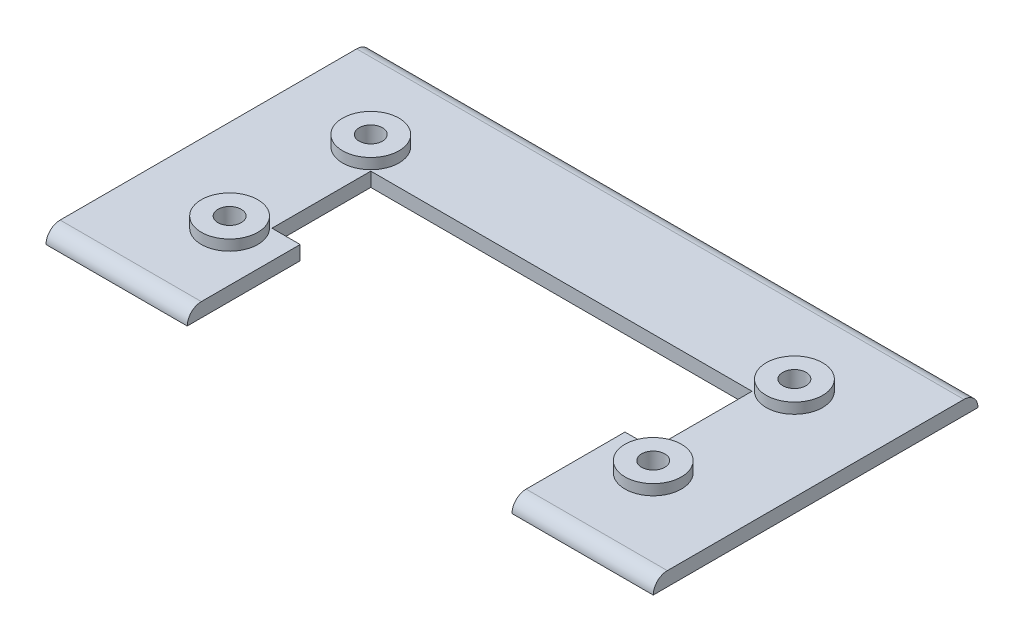
SolidWorks part; units mm, degrees
ref_plane "Front Plane" through (0, 0, 0) normal (0, 0, 1) x (1, 0, 0)
ref_plane "Top Plane" through (0, 0, 0) normal (0, 1, 0) x (1, 0, 0)
ref_plane "Right Plane" through (0, 0, 0) normal (1, 0, 0) x (0, 0, -1)
sketch "Sketch1" plane through (0, 0, 0) normal (0, 1, 0) x (1, 0, 0)
  line L1 (43, -23) -> (-43, -23)
  line L2 (43, -23) -> (43, 23)
  line L3 (43, 23) -> (-43, 23)
  line L4 (-43, -23) -> (-43, 23)
  line L5 (43, -23) -> (-43, 23) construction
  line L6 (43, 23) -> (-43, -23) construction
  point P0 (0, 0)
  dimension "D1" = 86
  dimension "D2" = 46
extrude "Boss-Extrude1" add sketch "Sketch1" along normal blind 2
sketch "Sketch2" plane through (0, 2, 0) normal (0, 1, 0) x (1, 0, 0)
  line L1 (27, -7) -> (-27, -7)
  line L2 (27, -7) -> (27, 7)
  line L3 (27, 7) -> (-27, 7)
  line L4 (-27, -7) -> (-27, 7)
  line L5 (27, -7) -> (-27, 7) construction
  line L6 (27, 7) -> (-27, -7) construction
  point P0 (0, 0)
  dimension "D1" = 14
  dimension "D2" = 54
extrude "Cut-Extrude1" cut sketch "Sketch2" against normal through all
sketch "Sketch4" plane through (0, 2, 0) normal (0, 1, 0) x (1, 0, 0)
  line L0 (27, 7) -> (-27, 7) construction
  line L1 (-27, 7) -> (-27, -7) construction
  line L2 (0, 23) -> (0, 0) construction
  line L3 (43, 23) -> (-43, 23) construction
  line L4 (0, 0) -> (-43, 0) construction
  line L5 (-43, 23) -> (-43, -23) construction
  circle A0 centre (-30, 10) radius 4
  circle A1 centre (-30, -10) radius 4
  circle A2 centre (30, -10) radius 4
  circle A3 centre (30, 10) radius 4
  dimension "D1" = 8
  dimension "D2" = 3
  dimension "D3" = 3
sketch "Sketch3" plane through (0, 2, 0) normal (0, 1, 0) x (1, 0, 0)
  line L0 (27, 7) -> (-27, 7) construction
  line L1 (-27, 7) -> (-27, -7) construction
  line L2 (0, 23) -> (0, 0) construction
  line L3 (43, 23) -> (-43, 23) construction
  line L4 (0, 0) -> (-43, 0) construction
  line L5 (-43, 23) -> (-43, -23) construction
  circle A0 centre (-30, 10) radius 1.65
  circle A1 centre (30, 10) radius 1.65
  circle A2 centre (30, -10) radius 1.65
  circle A3 centre (-30, -10) radius 1.65
  dimension "D1" = 3.3
  dimension "D2" = 3
  dimension "D3" = 3
extrude "Boss-Extrude2" add sketch "Sketch4" along normal blind 1.5
extrude "Cut-Extrude2" cut sketch "Sketch3" along normal up to surface (1.5 mm away) and the other way blind 10 up to face at (-30, 3.5, 6)
sketch "Sketch5" plane through (0, 0, 0) normal (0, -1, 0) x (1, 0, 0)
  line L0 (-37, -17) -> (-37, 17)
  line L1 (-37, 17) -> (37, 17)
  line L2 (37, 17) -> (37, -17)
  line L3 (37, -17) -> (-37, -17)
  line L4 (-35, -15) -> (-35, 15)
  line L5 (-35, 15) -> (35, 15)
  line L6 (35, 15) -> (35, -15)
  line L7 (35, -15) -> (-35, -15)
  line L8 (-27, -7) -> (-27, 7) construction
  line L9 (-27, 7) -> (27, 7) construction
  line L10 (27, 7) -> (27, -7) construction
  line L11 (27, -7) -> (-27, -7) construction
  dimension "D1" = 2
  dimension "D2" = 2
  dimension "D3" = 2
  dimension "D4" = 2
  dimension "D5" = 8
  dimension "D6" = 8
  dimension "D7" = 8
  dimension "D8" = 8
extrude "Cut-Extrude3" cut sketch "Sketch5" against normal blind 10 draft 45
fillet "Fillet1" radius 2 1 edges at (0, 2, -23) type face fillet first side face at (0, 1, -23) second side face at (30, 2, 14)
fillet "Fillet2" radius 2 1 edges at (0, 2, 23) type face fillet first side face at (30, 2, 14) second side face at (0, 1, 23)
sketch "Sketch6" plane through (0, 2, 0) normal (0, 1, 0) x (1, 0, 0)
  line L0 (-27, -7) -> (27, -7) construction
  line L1 (-23, -7) -> (23, -7)
  line L2 (-23, -7) -> (-23, -23)
  line L3 (-23, -23) -> (23, -23)
  line L4 (23, -7) -> (23, -23)
  line L5 (-43, -23) -> (43, -23) construction
  circle A0 centre (-30, -10) radius 4 construction
  circle A1 centre (30, -10) radius 4 construction
  dimension "D1" = 7
  dimension "D2" = 7
extrude "Cut-Extrude4" cut sketch "Sketch6" against normal blind 10
sketch "Sketch8" plane through (0, 0, 0) normal (0, -1, 0) x (1, 0, 0)
  line L0 (23, 17) -> (23, 15)
  line L1 (23, 15) -> (24.5, 15)
  line L2 (35, 15) -> (23, 15) construction
  line L3 (24.5, 15) -> (24.5, 17)
  line L4 (37, 17) -> (23, 17) construction
  line L5 (24.5, 17) -> (23, 17)
  line L6 (0, 0) -> (0, 15) construction
  line L7 (-24.5, 17) -> (-23, 17)
  line L8 (-24.5, 15) -> (-24.5, 17)
  line L9 (-23, 15) -> (-24.5, 15)
  line L10 (-23, 17) -> (-23, 15)
  dimension "D1" = 1.5
extrude "Boss-Extrude3" add sketch "Sketch8" against normal up to surface (2 mm away) up to face at (0, 2, 4.6667)
